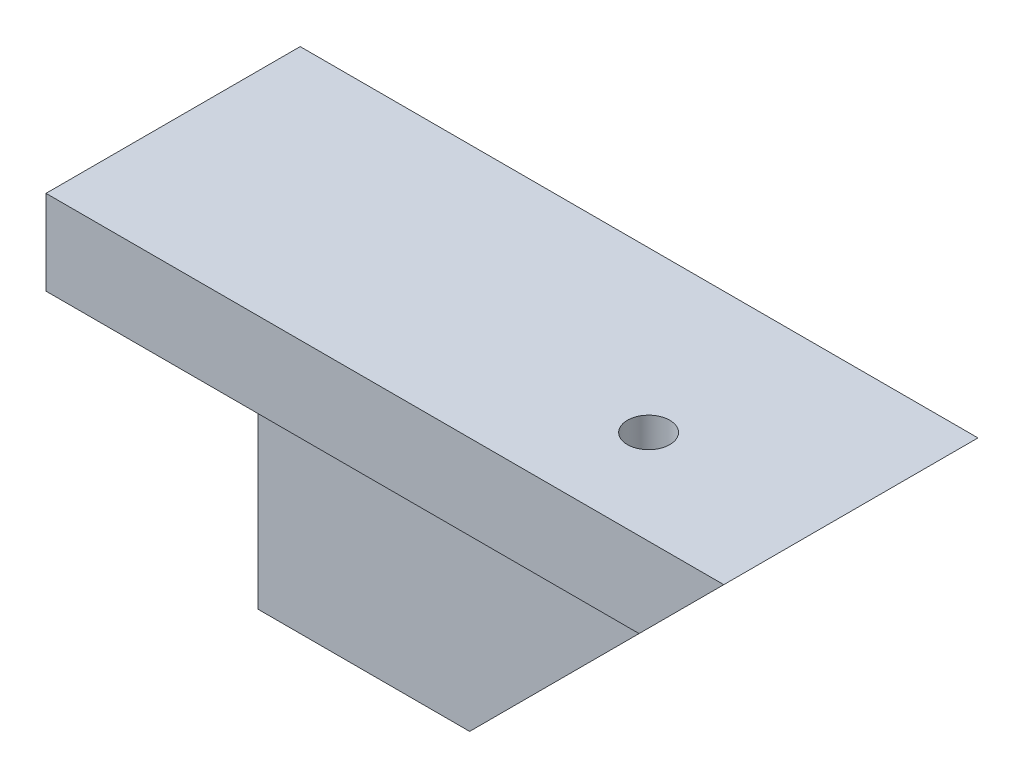
SolidWorks part; units mm, degrees
ref_plane "Front Plane" through (0, 0, 0) normal (0, 0, 1) x (1, 0, 0)
ref_plane "Top Plane" through (0, 0, 0) normal (0, 1, 0) x (1, 0, 0)
ref_plane "Right Plane" through (0, 0, 0) normal (1, 0, 0) x (0, 0, -1)
sketch "Sketch1" plane through (0, 0, 0) normal (0, 0, 1) x (1, 0, 0)
  line L0 (40, 27.5) -> (-15, -27.5)
  line L5 (-40, 27.5) -> (40, 27.5)
  line L6 (-40, 27.5) -> (-40, -27.5)
  line L7 (-40, -27.5) -> (-15, -27.5)
  line L10 (-40, -27.5) -> (40, 27.5) construction
  point P0 (0, 0)
  point P1 (-41.6675, -20.1998)
  dimension "D1" = 45
  dimension "D2" = 55
  dimension "D3" = 80
extrude "Boss-Extrude1" add sketch "Sketch1" along normal blind 5
sketch "Sketch3" plane through (0, 0, 5) normal (0, 0, 1) x (1, 0, 0)
  line L0 (-15, -27.5) -> (40, 27.5) construction
  line L1 (-40, 27.5) -> (40, 27.5)
  line L2 (-40, 27.5) -> (-40, 17.5)
  line L3 (-40, 17.5) -> (30, 17.5)
  line L4 (40, 27.5) -> (30, 17.5)
  point P4 (40, 20)
  point P5 (40, 3.4803)
  point P6 (24.2756, 4.2756)
  dimension "D1" = 10
extrude "Boss-Extrude2" add sketch "Sketch3" along normal blind 25
sketch "Sketch4" plane through (0, 27.5, 0) normal (0, 1, 0) x (1, 0, 0)
  line L0 (-40, -30) -> (-40, 0) construction
  line L1 (40, -30) -> (-40, -30) construction
  line L2 (40, -30) -> (40, -5) construction
  line L3 (40, -5) -> (-40, -5) construction
  line L4 (-40, -30) -> (-40, -5) construction
  line L5 (40, -30) -> (40, 0) construction
  line L6 (-40, 0) -> (40, 0) construction
  line L7 (-40, 0) -> (-40, 5) construction
  line L8 (-40, 5) -> (40, 5) construction
  line L9 (40, 0) -> (40, 5) construction
  circle A0 centre (20, -18.88) radius 2.5
  circle A1 centre (20, -18.88) radius 6.5 construction
  dimension "D3" = 13
  dimension "D4" = 5
  dimension "D1" = 25
  dimension "D2" = 5
  dimension "D5" = 23.88
  dimension "D6" = 20
extrude "Cut-Extrude1" cut sketch "Sketch4" against normal through all
